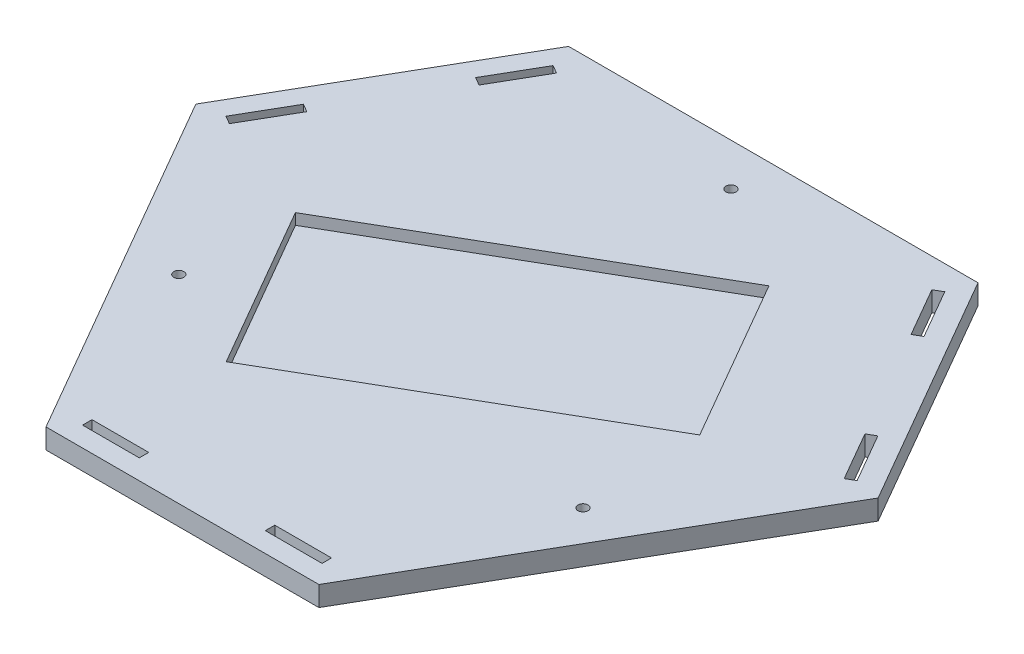
SolidWorks part; units mm, degrees
ref_plane "Front Plane" through (0, 0, 0) normal (0, 0, 1) x (1, 0, 0)
ref_plane "Top Plane" through (0, 0, 0) normal (0, 1, 0) x (1, 0, 0)
ref_plane "Right Plane" through (0, 0, 0) normal (1, 0, 0) x (0, 0, -1)
sketch "Sketch1" plane through (0, 0, 0) normal (0, 1, 0) x (1, 0, 0)
  line L0 (0, 200) -> (-173.2051, -100)
  line L1 (-173.2051, -100) -> (173.2051, -100)
  line L2 (173.2051, -100) -> (0, 200)
  line L4 (0, -175) -> (151.5544, 87.5)
  line L5 (151.5544, 87.5) -> (-151.5544, 87.5)
  line L6 (-151.5544, 87.5) -> (0, -175)
  circle A0 centre (0, 0) radius 200 construction
  circle A1 centre (0, 0) radius 100 construction
  circle A2 centre (0, 0) radius 175 construction
  circle A3 centre (0, 0) radius 87.5 construction
  dimension "D1" = 400
  dimension "D2" = 350
other "AlignGroup1"
extrude "Boss-Extrude1" add sketch "Sketch1" along normal blind 6.35 contours L0 L6 L1 L4 L2 L5 region at (0, 0, 0)
sketch "Sketch2" plane through (0, 6.35, 0) normal (0, 1, 0) x (1, 0, 0)
  line L0 (-43.3013, -100) -> (43.3013, -100) construction
  line L1 (-38, -90.7) -> (-20, -90.7)
  line L2 (-38, -90.7) -> (-38, -93.7)
  line L3 (-38, -93.7) -> (-20, -93.7)
  line L4 (-20, -90.7) -> (-20, -93.7)
  line L5 (0, -100) -> (0, 87.5) construction
  line L6 (64.9519, 87.5) -> (-64.9519, 87.5) construction
  line L7 (38, -90.7) -> (38, -93.7)
  line L8 (-86.6025, 50) -> (75.7772, -43.75) construction
  line L9 (-62.1466, 79.759) -> (-59.5485, 78.259)
  line L10 (20, -90.7) -> (20, -93.7)
  line L11 (-62.1466, 79.759) -> (-71.1466, 64.1705)
  line L12 (-71.1466, 64.1705) -> (-68.5485, 62.6705)
  line L13 (38, -93.7) -> (20, -93.7)
  line L14 (38, -90.7) -> (20, -90.7)
  line L15 (-59.5485, 78.259) -> (-68.5485, 62.6705)
  line L16 (-64.9519, 87.5) -> (-108.2532, 12.5) construction
  line L17 (43.3013, -100) -> (108.2532, 12.5) construction
  line L18 (-97.5485, 12.441) -> (-88.5485, 28.0295)
  line L19 (-91.1466, 29.5295) -> (-88.5485, 28.0295)
  line L20 (-100.1466, 13.941) -> (-91.1466, 29.5295)
  line L21 (-100.1466, 13.941) -> (-97.5485, 12.441)
  line L22 (86.6025, 50) -> (-75.7772, -43.75) construction
  line L23 (108.2532, 12.5) -> (64.9519, 87.5) construction
  line L24 (-108.2532, 12.5) -> (-43.3013, -100) construction
  line L25 (100.1466, 13.941) -> (91.1466, 29.5295)
  line L26 (59.5485, 78.259) -> (62.1466, 79.759)
  line L27 (59.5485, 78.259) -> (68.5485, 62.6705)
  line L28 (68.5485, 62.6705) -> (71.1466, 64.1705)
  line L29 (62.1466, 79.759) -> (71.1466, 64.1705)
  line L30 (88.5485, 28.0295) -> (91.1466, 29.5295)
  line L31 (97.5485, 12.441) -> (88.5485, 28.0295)
  line L32 (97.5485, 12.441) -> (100.1466, 13.941)
  point P4 (-29, -93.7)
  dimension "D1" = 18
  dimension "D2" = 3
  dimension "D3" = 6.3
  dimension "D4" = 38
  dimension "D5" = 6.3
  dimension "D6" = 18
  dimension "D7" = 3
  dimension "D8" = 38
  dimension "D9" = 18
  dimension "D10" = 3
  dimension "D11" = 38
  dimension "D12" = 6.3
extrude "Cut-Extrude1" cut sketch "Sketch2" against normal through all
sketch "Sketch3" plane through (0, 6.35, 0) normal (0, 1, 0) x (1, 0, 0)
  point P0 (0, 0)
ref_axis "Axis1" through (0, 0, 0) along (0, 1, 0)
sketch "Sketch4" plane through (0, 6.35, 0) normal (0, 1, 0) x (1, 0, 0)
  line L0 (108.2532, 12.5) -> (64.9519, 87.5) construction
  line L5 (-62.6314, -1.5192) -> (32.6314, 53.4808)
  line L6 (-62.6314, -1.5192) -> (-32.6314, -53.4808)
  line L7 (-32.6314, -53.4808) -> (62.6314, 1.5192)
  line L8 (32.6314, 53.4808) -> (62.6314, 1.5192)
  line L9 (-15, 25.9808) -> (15, -25.9808) construction
  line L10 (-47.6314, -27.5) -> (47.6314, 27.5) construction
  point P12 (0, 0)
  dimension "D1" = 110
  dimension "D2" = 60
extrude "Cut-Extrude2" cut sketch "Sketch4" against normal blind 3.5
sketch "Sketch8" plane through (0, 6.35, 0) normal (0, 1, 0) x (1, 0, 0)
  line L0 (0, 87.5) -> (0, 0) construction
  line L1 (64.9519, 87.5) -> (-64.9519, 87.5) construction
  line L2 (0, 0) -> (-75.7772, -43.75) construction
  line L3 (-108.2532, 12.5) -> (-43.3013, -100) construction
  line L4 (0, 0) -> (75.7772, -43.75) construction
  line L5 (43.3013, -100) -> (108.2532, 12.5) construction
  circle A0 centre (-64.1378, -37.03) radius 1.6
  circle A1 centre (64.1378, -37.03) radius 1.6
  circle A2 centre (0, 74.06) radius 1.6
  point P17 (0, 0)
  point P18 (0, 0)
  dimension "D1" = 3.2
  dimension "D2" = 13.44
  dimension "D3" = 13.44
  dimension "D4" = 13.44
extrude "Cut-Extrude3" cut sketch "Sketch8" against normal through all
